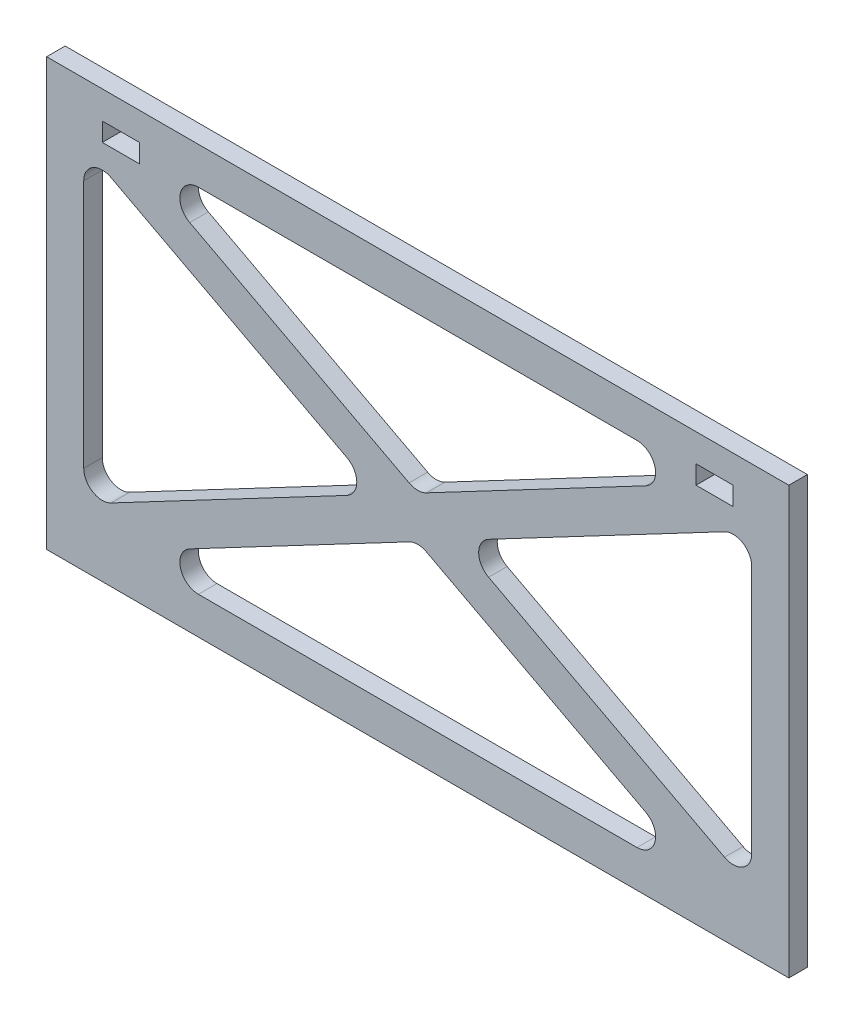
SolidWorks part; units mm, degrees
material "Beech"
ref_plane "Front Plane" through (0, 0, 0) normal (0, 0, 1) x (1, 0, 0)
ref_plane "Top Plane" through (0, 0, 0) normal (0, 1, 0) x (1, 0, 0)
ref_plane "Right Plane" through (0, 0, 0) normal (1, 0, 0) x (0, 0, -1)
sketch "Sketch1" plane through (0, 0, 0) normal (0, 0, 1) x (1, 0, 0)
  line L0 (91.44, 48.26) -> (-91.44, 48.26)
  line L1 (101.6, 58.42) -> (-101.6, 58.42)
  line L2 (101.6, 58.42) -> (101.6, -58.42)
  line L3 (101.6, -58.42) -> (-101.6, -58.42)
  line L4 (-101.6, 58.42) -> (-101.6, -58.42)
  line L5 (101.6, 58.42) -> (-101.6, -58.42) construction
  line L6 (101.6, -58.42) -> (-101.6, 58.42) construction
  line L7 (-91.44, 48.26) -> (-91.44, -48.26)
  line L8 (91.44, -48.26) -> (-91.44, -48.26)
  line L9 (91.44, 48.26) -> (91.44, -48.26)
  line L10 (-91.44, 48.26) -> (91.44, -48.26) construction
  line L11 (-91.44, -48.26) -> (91.44, 48.26) construction
  line L12 (-93.8111, 43.7673) -> (89.0689, -52.7527)
  line L13 (-89.0689, -52.7527) -> (93.8111, 43.7673)
  line L14 (-89.0689, 52.7527) -> (93.8111, -43.7673)
  line L15 (-93.8111, -43.7673) -> (89.0689, 52.7527)
  line L16 (0, 0) -> (0, 58.42) construction
  point P0 (0, 0)
  dimension "D1" = 116.84
  dimension "D2" = 203.2
  dimension "D3" = 10.16
  dimension "D4" = 5.08
  dimension "D5" = 5.08
extrude "Boss-Extrude1" add sketch "Sketch1" along normal blind 5.08 contours L1 L4 L3 L2 L0 L9 L8 L7 | L12 L15 L14 L0 L7 | L15 L14 L13 L9 L0 | L15 L12 L13 L14 | L15 L7 L8 L13 L12 | L14 L13 L12 L8 L9 | L14 L0 | L15 L0 region at (47.0953, 24.8558, 0) region at (-47.0953, 24.8558, 0) region at (0, 0, 0) region at (47.0953, -24.8558, 0) region at (-47.0953, -24.8558, 0) region at (99.256, 0, 0)
fillet "Fillet1" radius 5.08 12 edges at (10.8836, 0, 2.54) (91.44, -42.5159, 2.54) (80.5564, -48.26, 2.54) (-80.5564, -48.26, 2.54) (91.44, 42.5159, 2.54) (80.5564, 48.26, 2.54) (-80.5564, 48.26, 2.54) (0, -5.7441, 2.54) (-10.8836, 0, 2.54) (0, 5.7441, 2.54) (-91.44, -42.5159, 2.54) (-91.44, 42.5159, 2.54)
sketch "Sketch2" plane through (0, 0, 5.08) normal (0, 0, 1) x (1, 0, 0)
  line L0 (-86.36, 50.8) -> (-76.2, 50.8)
  line L1 (-86.36, 50.8) -> (-86.36, 45.72)
  line L2 (-86.36, 45.72) -> (-76.2, 45.72)
  line L3 (-76.2, 50.8) -> (-76.2, 45.72)
  line L4 (-86.36, 50.8) -> (-76.2, 45.72) construction
  line L5 (-86.36, 45.72) -> (-76.2, 50.8) construction
  line L6 (-101.6, 58.42) -> (-101.6, -58.42) construction
  line L7 (101.6, 58.42) -> (-101.6, 58.42) construction
  line L8 (0, 0) -> (0, 58.42) construction
  line L9 (86.36, 45.72) -> (76.2, 50.8) construction
  line L10 (86.36, 50.8) -> (76.2, 45.72) construction
  line L11 (76.2, 50.8) -> (76.2, 45.72)
  line L12 (86.36, 45.72) -> (76.2, 45.72)
  line L13 (86.36, 50.8) -> (86.36, 45.72)
  line L14 (86.36, 50.8) -> (76.2, 50.8)
  point P4 (-81.28, 48.26)
  point P16 (81.28, 48.26)
  dimension "D1" = 20.32
  dimension "D2" = 10.16
  dimension "D3" = 10.16
  dimension "D4" = 5.08
extrude "Cut-Extrude1" cut sketch "Sketch2" against normal through all both and the other way through all
